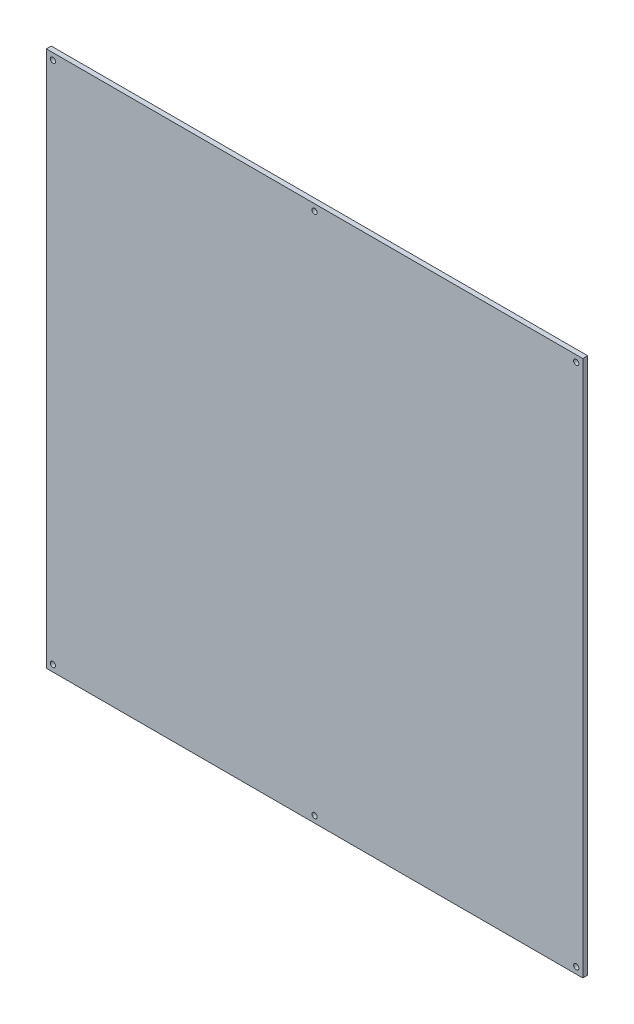
SolidWorks part; units mm, degrees
ref_plane "Alzado" through (0, 0, 0) normal (0, 0, 1) x (1, 0, 0)
ref_plane "Planta" through (0, 0, 0) normal (0, 1, 0) x (1, 0, 0)
ref_plane "Vista lateral" through (0, 0, 0) normal (1, 0, 0) x (0, 0, -1)
sketch "Croquis1" plane through (0, 0, 0) normal (0, 0, 1) x (1, 0, 0)
  line L1 (0, 0) -> (328, 0)
  line L2 (0, 0) -> (0, 328)
  line L3 (0, 328) -> (328, 328)
  line L4 (328, 0) -> (328, 328)
  dimension "D1" = 328
  dimension "D2" = 328
extrude "Saliente-Extruir1" add sketch "Croquis1" along normal blind 3
sketch "Croquis2" plane through (0, 0, 3) normal (0, 0, 1) x (1, 0, 0)
  line L0 (328, 328) -> (0, 328) construction
  line L1 (0, 328) -> (0, 0) construction
  line L2 (0, 164) -> (328, 164) construction
  line L3 (328, 0) -> (328, 328) construction
  circle A0 centre (4, 324) radius 1.6
  circle A1 centre (164, 324) radius 1.6
  circle A2 centre (324, 324) radius 1.6
  circle A3 centre (324, 4) radius 1.6
  circle A4 centre (164, 4) radius 1.6
  circle A5 centre (4, 4) radius 1.6
  dimension "D1" = 3.2
  dimension "D2" = 4
  dimension "D3" = 4
  dimension "D4" = 160
  dimension "D5" = 160
extrude "Cortar-Extruir1" cut sketch "Croquis2" against normal up to surface (3 mm away) up to face at (164, 164, 0)
